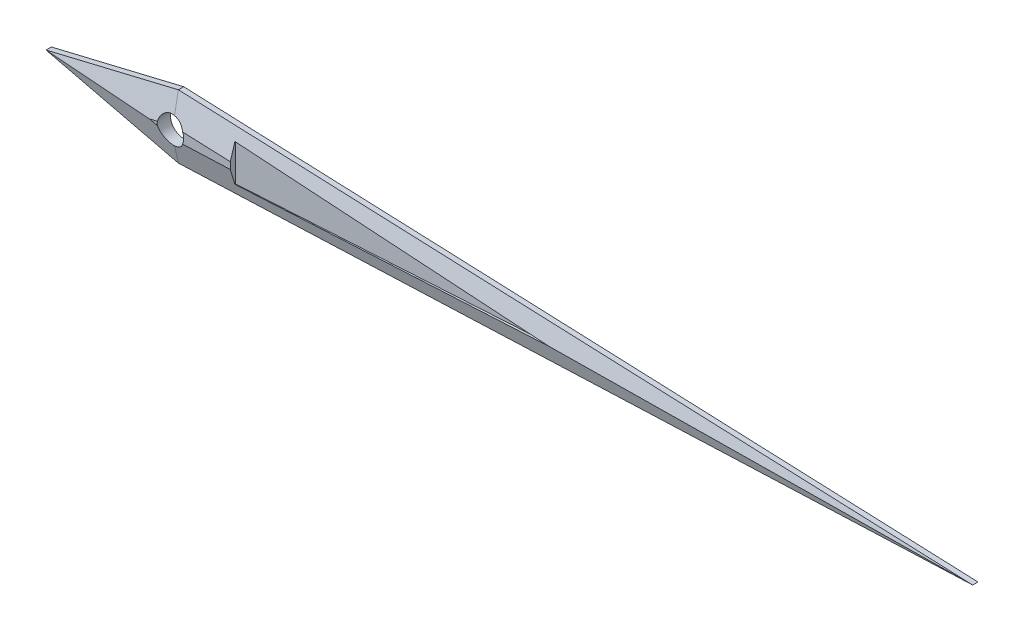
SolidWorks part; units mm, degrees
ref_plane "Front Plane" through (0, 0, 0) normal (0, 0, 1) x (1, 0, 0)
ref_plane "Top Plane" through (0, 0, 0) normal (0, 1, 0) x (1, 0, 0)
ref_plane "Right Plane" through (0, 0, 0) normal (1, 0, 0) x (0, 0, -1)
sketch "Sketch1" plane through (0, 0, 0) normal (0, 0, 1) x (1, 0, 0)
  line L1 (55, 0) -> (-55, 0) construction
  line L2 (0, -55) -> (0, 55) construction
  line L3 (0, 0.6) -> (-2.5, 0)
  line L4 (-2.5, 0) -> (0, -0.6)
  line L5 (0, -0.6) -> (15, 0)
  line L6 (0, 0.6) -> (15, 0)
  dimension "D1" = 17.5
  dimension "D2" = 2.5
extrude "Boss-Extrude1" add sketch "Sketch1" along normal blind 0.25
sketch "Sketch2" plane through (0, 0, 0.25) normal (0, 0, 1) x (1, 0, 0)
  circle A0 centre (0, 0) radius 0.25
  dimension "D1" = 0.5
extrude "Cut-Extrude1" cut sketch "Sketch2" against normal blind 0.25
chamfer "Chamfer1" distance 0.15 angle 73 2 edges at (7.5, 0.3, 0.25) (7.5, -0.3, 0.25) first distance on face at (7.5, 0.3, 0.125) first distance on face at (7.5, -0.3, 0.125)
chamfer "Chamfer2" distance 0.15 angle 73 2 edges at (-2.1268, 0.0896, 0.25) (-2.1268, -0.0896, 0.25) first distance on face at (-1.3507, 0.2758, 0.12) first distance on face at (-1.3507, -0.2758, 0.12)
sketch "Sketch3" plane through (0, 0, 0.25) normal (0, 0, 1) x (1, 0, 0)
  line L0 (1.1301, 0.35) -> (1.1301, -0.35)
  line L1 (1.1301, -0.35) -> (7.1045, 0)
  line L2 (0.1375, 0) -> (-0.1375, 0) construction
  line L3 (7.1045, 0) -> (1.1301, 0.35)
  dimension "D1" = 0.35
  dimension "D2" = 0.35
extrude "Cut-Extrude2" cut sketch "Sketch3" against normal blind 0.1
